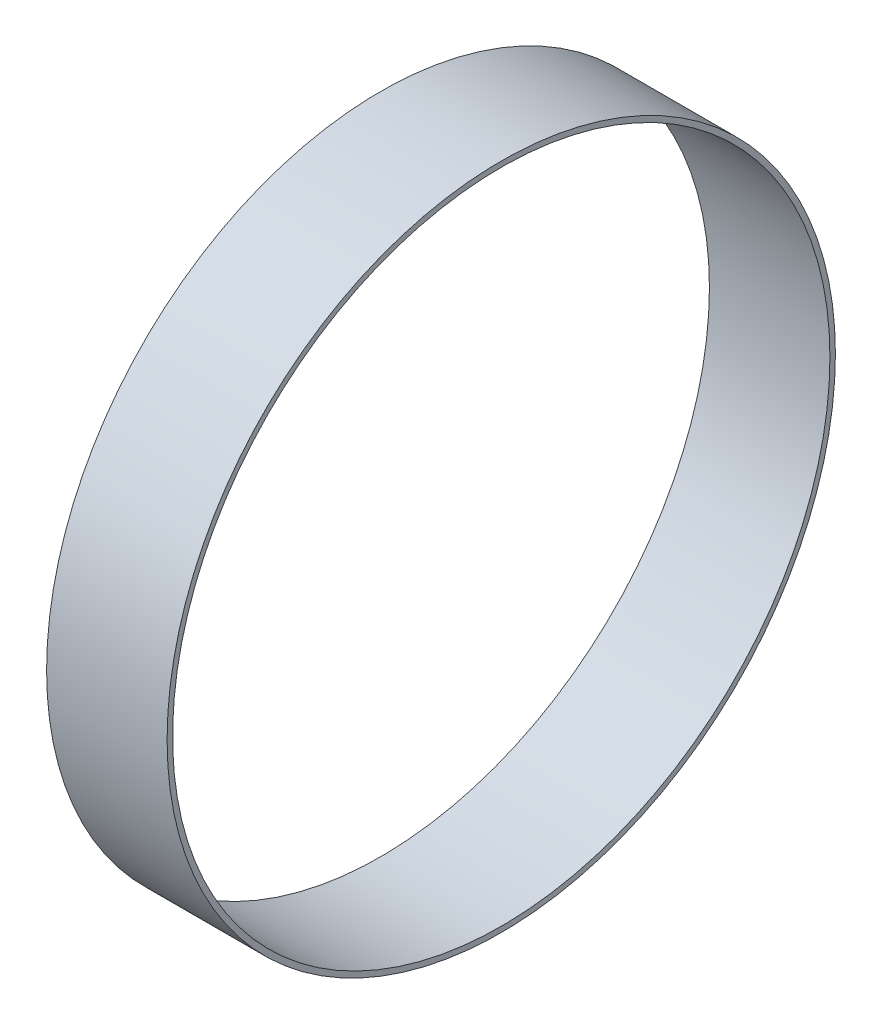
SolidWorks part; units mm, degrees
ref_plane "Front Plane" through (0, 0, 0) normal (0, 0, 1) x (1, 0, 0)
ref_plane "Top Plane" through (0, 0, 0) normal (0, 1, 0) x (1, 0, 0)
ref_plane "Right Plane" through (0, 0, 0) normal (1, 0, 0) x (0, 0, -1)
sketch "Sketch1" plane through (0, 0, 0) normal (1, 0, 0) x (0, 0, -1)
  line L0 (-190.5, 0) -> (-193.675, 0) construction
  circle A0 centre (0, 0) radius 193.675
  circle A1 centre (0, 0) radius 190.5
  dimension "D2" = 381
  dimension "D1" = 3.175
extrude "Boss-Extrude1" add sketch "Sketch1" along normal blind 69.85
